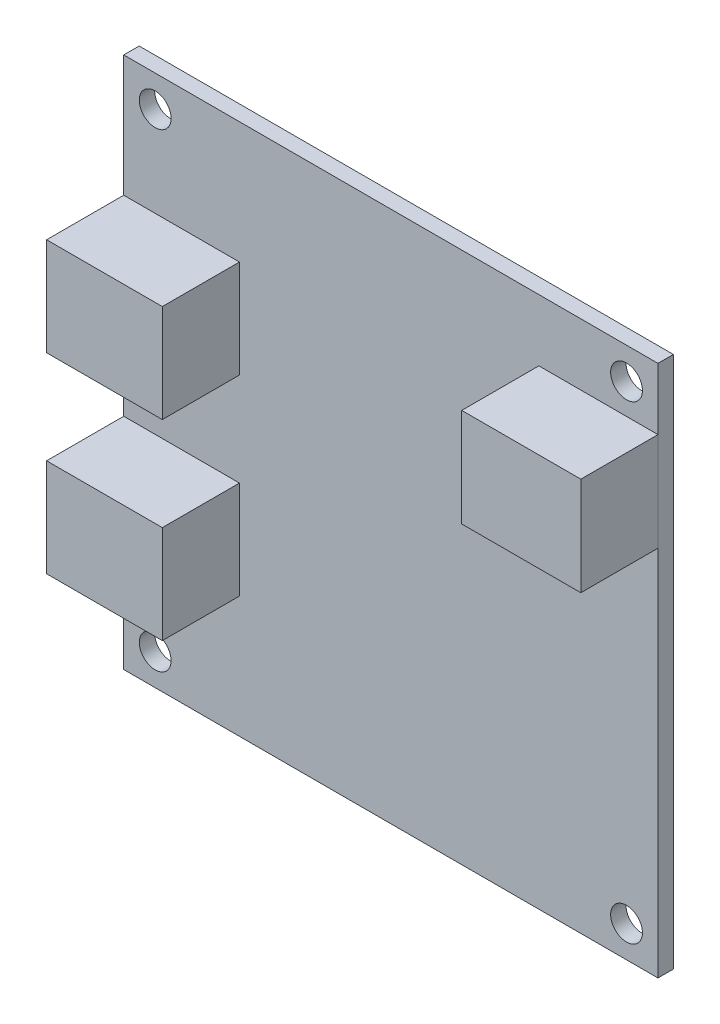
SolidWorks part; units mm, degrees
ref_plane "정면" through (0, 0, 0) normal (0, 0, 1) x (1, 0, 0)
ref_plane "윗면" through (0, 0, 0) normal (0, 1, 0) x (1, 0, 0)
ref_plane "우측면" through (0, 0, 0) normal (1, 0, 0) x (0, 0, -1)
sketch "스케치1" plane through (0, 0, 0) normal (0, 0, 1) x (1, 0, 0)
  line L0 (-27.7, -4.85) -> (-15.7, -4.85)
  line L1 (-27.7, -27.6) -> (27.7, -27.6)
  line L2 (-27.7, -27.6) -> (-27.7, 27.6)
  line L3 (-27.7, 27.6) -> (27.7, 27.6)
  line L4 (27.7, -27.6) -> (27.7, 27.6)
  line L5 (-27.7, -27.6) -> (27.7, 27.6) construction
  line L6 (-27.7, 27.6) -> (27.7, -27.6) construction
  line L7 (-15.7, -4.85) -> (-15.7, -15)
  line L8 (-15.7, -15) -> (-27.7, -15)
  line L9 (0, 0) -> (62.8852, 0) construction
  line L10 (-15.7, 15) -> (-27.7, 15)
  line L11 (-15.7, 4.85) -> (-15.7, 15)
  line L12 (-27.7, 4.85) -> (-15.7, 4.85)
  line L13 (0, -52.3833) -> (0, 52.3833) construction
  line L14 (27.7, 21.2) -> (15.35, 21.2)
  line L15 (15.35, 21.2) -> (15.35, 11)
  line L16 (15.35, 11) -> (27.7, 11)
  circle A0 centre (24.4382, 24.35) radius 1.65
  circle A1 centre (24.4382, -24.35) radius 1.65
  circle A2 centre (-24.4382, -24.35) radius 1.65
  circle A3 centre (-24.4382, 24.35) radius 1.65
  point P0 (0, 0)
  dimension "D6" = 3.3
  dimension "D7" = 3.25
  dimension "D1" = 55.2
  dimension "D2" = 55.4
  dimension "D3" = 10.15
  dimension "D4" = 12
  dimension "D5" = 12.6
  dimension "D8" = 10.2
  dimension "D9" = 12.35
  dimension "D10" = 6.4
extrude "보스-돌출1" add sketch "스케치1" against normal blind 1.6 contours L2 L12 L11 L10 | L8 L7 L0 L2 | L16 L15 L14 L4 L3 L2 L10 L11 L12 L0 L7 L8 L1 A1 A0 A2 A3 | L15 L16 L4 L14 region at (0.97, -0.7641, 0) region at (-21.7, -9.925, 0) region at (-21.7, 9.925, 0) region at (21.525, 16.1, 0)
extrude "보스-돌출2" add sketch "스케치1<3>" along normal blind 8 separate body contours L2 L12 L11 L10 | L8 L7 L0 L2 region at (-21.7, -9.925, 0) region at (-21.7, 9.925, 0)
sketch "스케치1<3>" plane through (0, 0, 0) normal (0, 0, 1) x (1, 0, 0) same geometry as "스케치1"
extrude "보스-돌출3" add sketch "스케치1<4>" along normal blind 8 separate body contours L15 L16 L4 L14 region at (21.525, 16.1, 0)
sketch "스케치1<4>" plane through (0, 0, 0) normal (0, 0, 1) x (1, 0, 0) same geometry as "스케치1"
